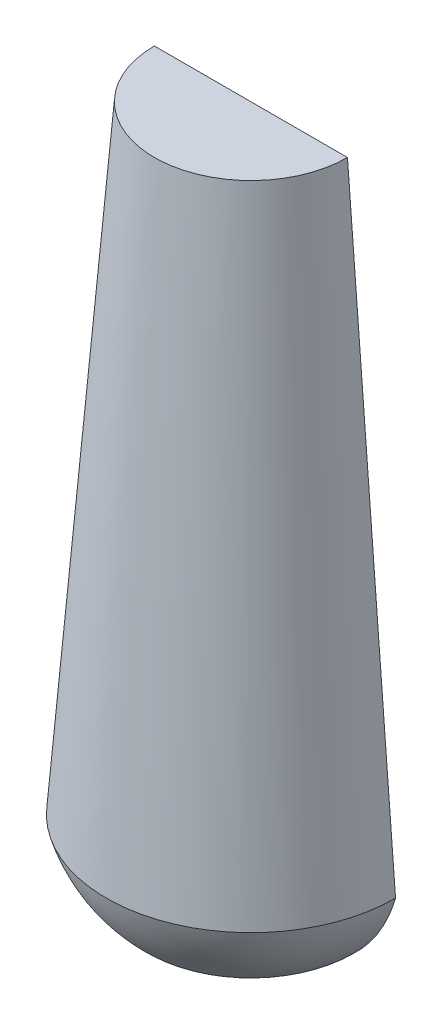
SolidWorks part; units mm, degrees
ref_plane "Front Plane" through (0, 0, 0) normal (0, 0, 1) x (1, 0, 0)
ref_plane "Top Plane" through (0, 0, 0) normal (0, 1, 0) x (1, 0, 0)
ref_plane "Right Plane" through (0, 0, 0) normal (1, 0, 0) x (0, 0, -1)
sketch "Sketch1" plane through (0, 0, 0) normal (0, 0, 1) x (1, 0, 0)
  line L0 (27.686, 0) -> (22.606, 0)
  line L1 (22.606, 0) -> (22.606, 1.8288)
  line L2 (28.829, 4.191) -> (22.606, 4.191)
  line L3 (22.606, 4.191) -> (22.606, 5.8928)
  line L4 (22.606, 5.8928) -> (30.607, 5.8928)
  line L5 (35.8598, 16.2226) -> (0, 16.2226)
  line L6 (0, 16.2226) -> (0, 185.547)
  line L7 (0, 185.547) -> (26.0985, 185.547)
  line L8 (26.0985, 185.547) -> (39.0906, 18.669)
  line L9 (36.5429, 18.669) -> (35.3733, 33.6922) construction
  line L10 (27.686, 0) -> (-9.2457, -34.4394) construction
  line L11 (39.0906, 18.669) -> (56.6975, 77.9254) construction
  line L12 (36.7195, 19.0327) -> (35.0001, 13.4124) construction
  line L13 (32.6347, 8.1905) -> (28.5793, 3.5951) construction
  line L14 (30.8955, 5.835) -> (26.7625, 2.547) construction
  line L15 (22.606, 1.8288) -> (0, 1.8288) construction
  spline S0 degree 3 poles (27.686, 0) (33.0499, 5.0019) (36.8721, 11.2026) (39.0906, 18.669) knots 0 0 0 0 1 1 1 1
  spline S1 degree 3 poles (22.606, 1.8288) (25.0412, 1.8288) (27.1069, 2.821) (28.829, 4.191) knots 0 0 0 0 0.286843 0.286843 0.286843 0.286843
  spline S2 degree 3 poles (30.607, 5.8928) (33.1416, 8.7649) (34.7852, 12.7099) (35.8598, 16.2226) knots 0.392904 0.392904 0.392904 0.392904 0.881974 0.881974 0.881974 0.881974
  dimension "D1" = 185.547
  dimension "D2" = 39.0906
  dimension "D3" = 22.606
  dimension "D4" = 5.08
  dimension "D5" = 1.8288
  dimension "D6" = 2.3622
  dimension "D7" = 6.223
  dimension "D8" = 8.001
  dimension "D9" = 1.7018
  dimension "D10" = 26.0985
  dimension "D11" = 18.669
  dimension "D12" = 2.54
  dimension "D13" = 2.54
  dimension "D14" = 43
  dimension "D15" = 21
revolve "Revolve1" add sketch "Sketch1" angle 180 about L6 reverse direction yes
